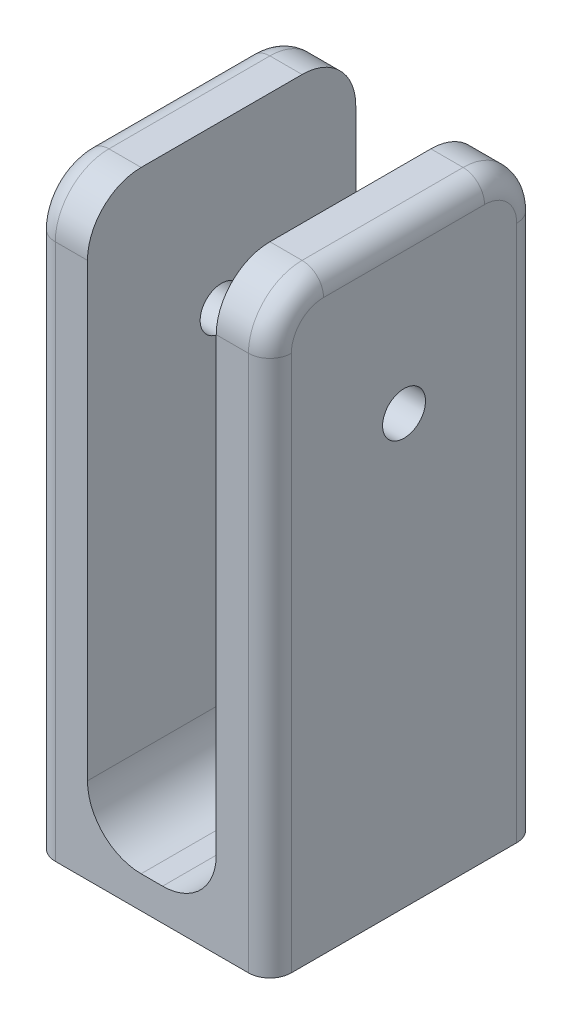
SolidWorks part; units mm, degrees
ref_plane "Front Plane" through (0, 0, 0) normal (0, 0, 1) x (1, 0, 0)
ref_plane "Top Plane" through (0, 0, 0) normal (0, 1, 0) x (1, 0, 0)
ref_plane "Right Plane" through (0, 0, 0) normal (1, 0, 0) x (0, 0, -1)
sketch "Sketch1" plane through (0, 0, 0) normal (0, 1, 0) x (1, 0, 0)
  line L0 (11, 12.5) -> (-11, 12.5)
  line L1 (11, 12.5) -> (11, -12.5)
  line L2 (-11, 12.5) -> (-11, -12.5)
  line L3 (11, -12.5) -> (-11, -12.5)
  line L4 (11, 12.5) -> (-11, -12.5) construction
  line L5 (-11, 12.5) -> (11, -12.5) construction
  line L7 (-11, 12.5) -> (-6, 12.5)
  line L8 (-11, 12.5) -> (-11, -12.5)
  line L9 (-11, -12.5) -> (-6, -12.5)
  line L10 (-6, 12.5) -> (-6, -12.5)
  line L11 (11, 12.5) -> (6, 12.5)
  line L12 (11, 12.5) -> (11, -12.5)
  line L13 (11, -12.5) -> (6, -12.5)
  line L14 (6, 12.5) -> (6, -12.5)
  point P1 (0, 0)
  dimension "D1" = 25
  dimension "D2" = 22
  dimension "D3" = 5
  dimension "D4" = 5
extrude "Boss-Extrude1" add sketch "Sketch1" along normal blind 3 contours L14 L0 L10 L3 region at (0, 0, 0)
extrude "Boss-Extrude2" add sketch "Sketch1<3>" along normal blind 55 contours L10 L0 L2 L3 | L0 L14 L3 L1 region at (8.5, 0, 0) region at (-8.5, 0, 0)
sketch "Sketch1<3>" plane through (0, 0, 0) normal (0, 1, 0) x (1, 0, 0) same geometry as "Sketch1"
fillet "Fillet1" radius 5 6 edges at (8.5, 55, -12.5) (-8.5, 55, -12.5) (-8.5, 55, 12.5) (8.5, 55, 12.5) (6, 3, 0) (-6, 3, 0)
fillet "Fillet2" radius 2 10 edges at (-11, 25, -12.5) (-11, 53.5355, -11.0355) (-11, 55, 0) (-11, 53.5355, 11.0355) (11, 25, -12.5) (11, 53.5355, -11.0355) (11, 55, 0) (11, 53.5355, 11.0355) (-11, 25, 12.5) (11, 25, 12.5)
hole_wizard "Ø4.0mm Dowel Hole3" positions "Sketch6" profile "Sketch7" hole size "Ø4.0" standard "ANSI Metric" end condition through all
sketch "Sketch6" plane through (-11, 0, 0) normal (-1, 0, 0) x (0, 0, 1)
  point P0 (0, 39.9011)
sketch "Sketch7" plane through (-11, 39.9011, 0) normal (0, 1, 0) x (0, 0, 1)
  line L0 (0, 0) -> (0, 22)
  line L1 (0, 22) -> (2, 22)
  line L2 (2, 22) -> (2, 0)
  line L5 (2, 0) -> (0, 0)
  line L11 (0, -6.35) -> (0, 107.95) construction
  dimension "Thru Hole Dia." = 4
  dimension "Thru Hole Depth" = 22
